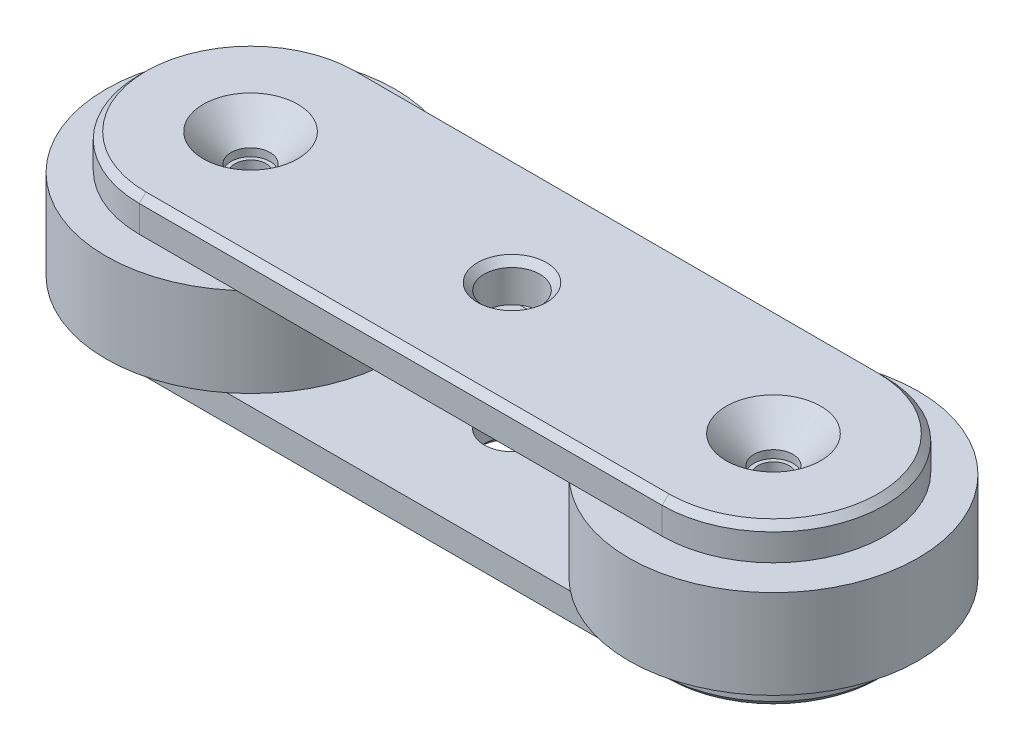
SolidWorks part; units mm, degrees
ref_plane "Front Plane" through (0, 0, 0) normal (0, 0, 1) x (1, 0, 0)
ref_plane "Top Plane" through (0, 0, 0) normal (0, 1, 0) x (1, 0, 0)
ref_plane "Right Plane" through (0, 0, 0) normal (1, 0, 0) x (0, 0, -1)
sketch "Sketch1" plane through (0, 0, 0) normal (0, 1, 0) x (1, 0, 0)
  line L0 (23.5, 0) -> (-23.5, 0) construction
  line L1 (23.5, -10) -> (-23.5, -10)
  line L2 (23.5, 10) -> (-23.5, 10)
  arc A0 (23.5, -10) -> (23.5, 10) centre (23.5, 0) ccw
  arc A1 (-23.5, 10) -> (-23.5, -10) centre (-23.5, 0) ccw
  circle A2 centre (0, 0) radius 2.5
  circle A3 centre (-23.5, 0) radius 5 construction
  circle A4 centre (23.5, 0) radius 5 construction
  point P2 (0, 0)
  dimension "D1" = 10
  dimension "D3" = 5
  dimension "D4" = 10
  dimension "D2" = 47
extrude "Boss-Extrude1" add sketch "Sketch1" along normal blind 3
sketch "Sketch10" plane through (0, 3, 0) normal (0, 1, 0) x (1, 0, 0)
  circle A0 centre (-23.5, 0) radius 7.5
  circle A1 centre (23.5, 0) radius 7.5
  dimension "D1" = 15
extrude "Boss-Extrude6" add sketch "Sketch10" along normal blind 0.2
sketch "Sketch11" plane through (0, 3.2, 0) normal (0, 1, 0) x (1, 0, 0)
  circle A0 centre (-23.5, 0) radius 4.95
  circle A1 centre (23.5, 0) radius 4.95
  dimension "D1" = 9.9
extrude "Boss-Extrude8" add sketch "Sketch11" along normal blind 8
sketch "Sketch12" plane through (0, 3.2, 0) normal (0, 1, 0) x (1, 0, 0)
  circle A0 centre (-23.5, 0) radius 5
  circle A1 centre (-23.5, 0) radius 13
  dimension "D1" = 26
  dimension "D2" = 10
extrude "Boss-Extrude9" add sketch "Sketch12" along normal blind 8 separate body
mirror "Mirror3" about plane through (0, 0, 0) normal (1, 0, 0) of bodies 113
sketch "Sketch13" plane through (0, 11.2, 0) normal (0, 1, 0) x (1, 0, 0)
  circle A0 centre (-23.5, 0) radius 1.4
  circle A1 centre (23.5, 0) radius 1.4
  dimension "D1" = 2.8
extrude "Cut-Extrude6" cut sketch "Sketch13" against normal through all
ref_plane "Plane1" through (0, 11.4, 0) normal (0, 1, 0) x (1, 0, 0)
sketch "Sketch14" plane through (0, 11.4, 0) normal (0, 1, 0) x (1, 0, 0)
  line L2 (-23.5, -10) -> (23.5, -10)
  line L3 (23.5, 10) -> (-23.5, 10)
  line L4 (-23.5, -10) -> (23.5, -10)
  line L5 (23.5, 10) -> (-23.5, 10)
  circle A0 centre (0, 0) radius 2.5 construction
  circle A1 centre (0, 0) radius 2.5
  arc A2 (23.5, -10) -> (23.5, 10) centre (23.5, 0) ccw
  arc A3 (-23.5, 10) -> (-23.5, -10) centre (-23.5, 0) ccw
  arc A4 (23.5, -10) -> (23.5, 10) centre (23.5, 0) ccw
  arc A5 (-23.5, 10) -> (-23.5, -10) centre (-23.5, 0) ccw
  circle A8 centre (-23.5, 0) radius 1.75
  circle A9 centre (23.5, 0) radius 1.75
  dimension "D2" = 3.5
  dimension "D1" = 0
extrude "Boss-Extrude10" add sketch "Sketch14" along normal blind 3 separate body
sketch "Sketch15" plane through (0, 11.4, 0) normal (0, -1, 0) x (1, 0, 0)
  circle A2 centre (23.5, 0) radius 7.5 construction
  circle A3 centre (-23.5, 0) radius 7.5 construction
  circle A4 centre (-23.5, 0) radius 1.75 construction
  circle A5 centre (23.5, 0) radius 1.75 construction
  circle A6 centre (23.5, 0) radius 7.5
  circle A7 centre (-23.5, 0) radius 7.5
  circle A8 centre (-23.5, 0) radius 1.75
  circle A9 centre (23.5, 0) radius 1.75
extrude "Boss-Extrude11" add sketch "Sketch15" along normal blind 0.2
chamfer "Chamfer1" distance 2.5 angle 45 2 edges at (-23.5, 14.4, 1.75) (23.5, 14.4, 1.75)
chamfer "Chamfer2" distance 0.6 angle 45 5 edges at (0, 14.4, 10) (33.5, 14.4, 0) (-33.5, 14.4, 0) (0, 14.4, -10) (0, 14.4, 2.5)
sketch "Sketch16" plane through (0, 3, 0) normal (0, 1, 0) x (1, 0, 0)
  line L0 (-10, 0) -> (-2.5, 0)
  line L1 (2.5, 0) -> (10, 0)
  arc A0 (10, 0) -> (-10, 0) centre (0, 0) ccw
  circle A1 centre (0, 0) radius 2.5 construction
  arc A2 (2.5, 0) -> (-2.5, 0) centre (0, 0) ccw
  point P1 (0, 9.8983)
  point P4 (-9.9846, 0.5556)
  dimension "D1" = 20
extrude "Boss-Extrude12" add sketch "Sketch16" along normal blind 0.5
sketch "Sketch17" plane through (0, 11.4, 0) normal (0, -1, 0) x (1, 0, 0)
  line L4 (-2.5, 0) -> (-10, 0)
  line L5 (10, 0) -> (2.5, 0)
  line L6 (-2.5, 0) -> (-10, 0)
  line L7 (10, 0) -> (2.5, 0)
  arc A5 (-10, 0) -> (10, 0) centre (0, 0) ccw
  arc A6 (-2.5, 0) -> (2.5, 0) centre (0, 0) ccw
  arc A8 (-10, 0) -> (10, 0) centre (0, 0) ccw
  arc A9 (-2.5, 0) -> (2.5, 0) centre (0, 0) ccw
  dimension "D1" = 0
extrude "Boss-Extrude13" add sketch "Sketch17" along normal blind 0.5
chamfer "Chamfer3" distance 0.6 angle 45 7 edges at (23.5, 0, 1.4) (0, 0, 2.5) (-23.5, 0, 1.4) (33.5, 0, 0) (0, 0, -10) (0, 0, 10) (-33.5, 0, 0)
equation "\"D2@Sketch1\"=73-26"
